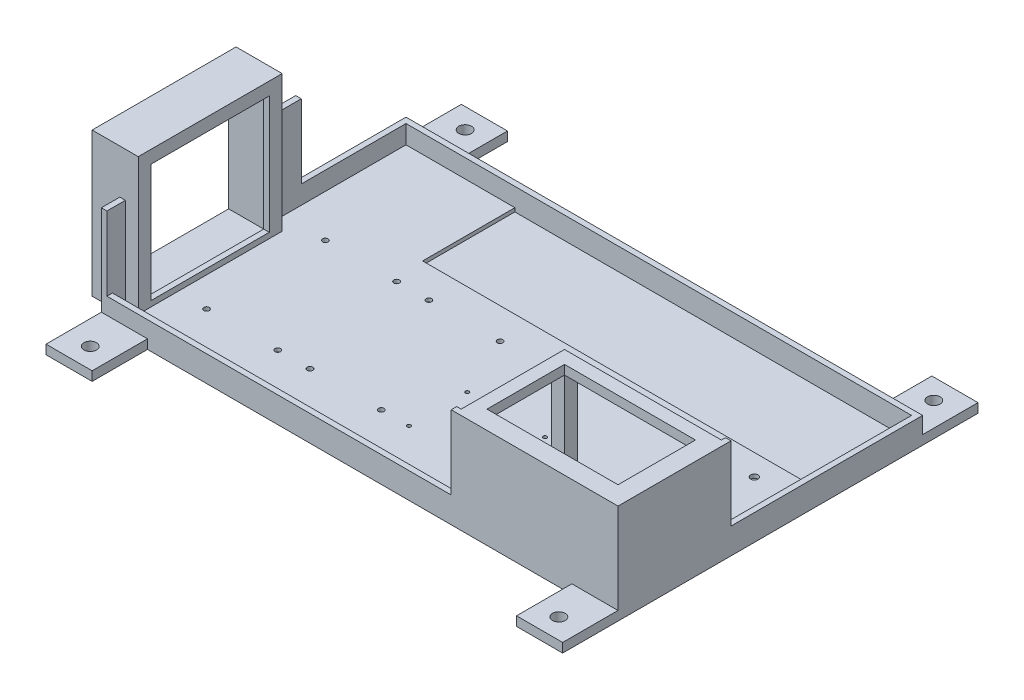
SolidWorks part; units mm, degrees
ref_plane "Front Plane" through (0, 0, 0) normal (0, 0, 1) x (1, 0, 0)
ref_plane "Top Plane" through (0, 0, 0) normal (0, 1, 0) x (1, 0, 0)
ref_plane "Right Plane" through (0, 0, 0) normal (1, 0, 0) x (0, 0, -1)
sketch "Sketch1" plane through (0, 0, 0) normal (0, 1, 0) x (1, 0, 0)
  line L1 (-140, -82.55) -> (140, -82.55)
  line L2 (-140, -82.55) -> (-140, 82.55)
  line L3 (-140, 82.55) -> (140, 82.55)
  line L4 (140, -82.55) -> (140, 82.55)
  line L5 (-140, -82.55) -> (140, 82.55) construction
  line L6 (-140, 82.55) -> (140, -82.55) construction
  point P0 (0, 0)
  dimension "D1" = 165.1
  dimension "D2" = 280
extrude "Floor" add sketch "Sketch1" along normal blind 4
sketch "Sketch2" plane through (0, 4, 0) normal (0, 1, 0) x (1, 0, 0)
  line L0 (137, -79.55) -> (137, 79.55)
  line L1 (137, 79.55) -> (-137, 79.55)
  line L2 (-137, 79.55) -> (-137, -79.55)
  line L3 (-137, -79.55) -> (137, -79.55)
  line L4 (140, -82.55) -> (140, 82.55)
  line L5 (140, 82.55) -> (-140, 82.55)
  line L6 (-140, 82.55) -> (-140, -82.55)
  line L7 (-140, -82.55) -> (140, -82.55)
  line L8 (140, -82.55) -> (140, 82.55)
  line L9 (140, 82.55) -> (-140, 82.55)
  line L10 (-140, 82.55) -> (-140, -82.55)
  line L11 (-140, -82.55) -> (140, -82.55)
  dimension "D1" = 0
  dimension "D2" = 3
extrude "Wall" add sketch "Sketch2" along normal blind 10
sketch "Sketch4" plane through (0, 4, 0) normal (0, 1, 0) x (1, 0, 0)
  line L0 (130, -30.55) -> (59, -30.55)
  line L1 (137, -79.55) -> (52, -79.55)
  line L2 (137, -79.55) -> (137, -23.55)
  line L3 (137, -23.55) -> (52, -23.55)
  line L4 (52, -79.55) -> (52, -23.55)
  line L5 (59, -72.55) -> (59, -30.55)
  line L6 (130, -72.55) -> (59, -72.55)
  line L7 (130, -72.55) -> (130, -30.55)
  dimension "D1" = 85
  dimension "D2" = 56
  dimension "D3" = 7
extrude "Rpi stand" add sketch "Sketch4" along normal blind 5 from offset 45
sketch "Sketch7" plane through (0, 14, 0) normal (0, 1, 0) x (1, 0, 0)
  line L0 (-137, 79.55) -> (-137, -79.55) construction
  line L1 (-140, -82.55) -> (-137, -82.55)
  line L2 (-140, -82.55) -> (-140, 22.7839)
  line L3 (-140, 22.7839) -> (-137, 22.7839)
  line L4 (-137, -82.55) -> (-137, 22.7839)
  line L5 (-137, -79.55) -> (137, -79.55) construction
  line L6 (140, -82.55) -> (49.6123, -82.55)
  line L7 (140, -82.55) -> (140, -79.55)
  line L8 (137, -79.55) -> (49.6123, -79.55)
  line L9 (49.6123, -82.55) -> (49.6123, -79.55)
  line L10 (137, -79.55) -> (137, 79.55) construction
  line L12 (140, -79.55) -> (140, -21.3069)
  line L13 (140, -21.3069) -> (137, -21.3069)
  line L14 (137, -79.55) -> (137, -21.3069)
  line L15 (-137, -79.55) -> (137, -79.55) construction
extrude "Temp support" add sketch "Sketch7" along normal blind 40
sketch "Sketch3" plane through (0, 0, 0) normal (0, 1, 0) x (1, 0, 0)
  line L0 (-127, 101.6) -> (127, 101.6) construction
  line L1 (-140, 82.55) -> (-115, 82.55)
  line L2 (-140, 82.55) -> (-140, 112.55)
  line L3 (-140, 112.55) -> (-115, 112.55)
  line L4 (-115, 82.55) -> (-115, 112.55)
  line L5 (140, 82.55) -> (115, 82.55)
  line L6 (140, 82.55) -> (140, 112.55)
  line L7 (140, 112.55) -> (115, 112.55)
  line L8 (115, 82.55) -> (115, 112.55)
  line L9 (-140, -82.55) -> (-115, -82.55)
  line L10 (-140, -82.55) -> (-140, -112.55)
  line L11 (-140, -112.55) -> (-115, -112.55)
  line L12 (-115, -82.55) -> (-115, -112.55)
  line L13 (140, -82.55) -> (115, -82.55)
  line L14 (140, -82.55) -> (140, -112.55)
  line L15 (140, -112.55) -> (115, -112.55)
  line L16 (115, -82.55) -> (115, -112.55)
  line L17 (127, 101.6) -> (127, -101.6) construction
  line L18 (127, -101.6) -> (-127, -101.6) construction
  line L19 (-127, -101.6) -> (-127, 101.6) construction
  line L20 (-140, 30.6215) -> (140, 30.6215) construction
  line L22 (140, -21.3069) -> (140, 82.55) construction
  line L23 (0, 101.6) -> (0, -101.6) construction
  line L24 (-140, 22.7839) -> (-140, -82.55) construction
  line L25 (140, -21.3069) -> (140, 82.55) construction
  line L26 (-137, -82.55) -> (49.6123, -82.55) construction
  circle A0 centre (-127, 101.6) radius 3.429
  circle A1 centre (127, 101.6) radius 3.429
  circle A2 centre (127, -101.6) radius 3.429
  circle A3 centre (-127, -101.6) radius 3.429
  point P28 (-127.5, -82.55)
  point P29 (-115, -97.55)
  point P30 (127.5, -82.55)
  point P31 (-115, 97.55)
  dimension "D5" = 6.858
  dimension "D1" = 25
  dimension "D2" = 25
  dimension "D3" = 30
  dimension "D4" = 30
  dimension "D6" = 203.2
  dimension "D7" = 254
extrude "Brackets" add sketch "Sketch3" along normal blind 5
sketch "Sketch5" plane through (-140, 0, 0) normal (-1, 0, 0) x (0, 0, 1)
  line L0 (-5.45, 78) -> (72.55, 78)
  line L1 (-1.45, 4) -> (68.55, 4)
  line L2 (-1.45, 4) -> (-1.45, 74)
  line L3 (-1.45, 74) -> (68.55, 74)
  line L4 (68.55, 4) -> (68.55, 74)
  line L5 (72.55, 0) -> (72.55, 78)
  line L6 (-5.45, 0) -> (72.55, 0)
  line L7 (-5.45, 0) -> (-5.45, 78)
  line L9 (112.55, 5) -> (112.55, 0) construction
  line L11 (-79.55, 4) -> (79.55, 4) construction
  dimension "D1" = 70
  dimension "D2" = 70
  dimension "D5" = 40
  dimension "D3" = 4
extrude "Fan Holder" add sketch "Sketch5" along normal blind 15 and the other way blind 10
sketch "Sketch8" plane through (-140, 0, 0) normal (-1, 0, 0) x (0, 0, 1)
  line L4 (-1.45, 54) -> (-1.45, 4)
  line L5 (-1.45, 4) -> (68.55, 4)
  line L6 (68.55, 4) -> (68.55, 54)
  line L7 (68.55, 54) -> (-1.45, 54)
  line L8 (-1.45, 54) -> (-1.45, 4)
  line L9 (-1.45, 4) -> (68.55, 4)
  line L10 (68.55, 4) -> (68.55, 54)
  line L15 (68.55, 54) -> (-1.45, 54)
  dimension "D1" = 0
extrude "Fan hole" cut sketch "Sketch8" against normal up to next (3 mm away)
sketch "Sketch11" plane through (-130, 0, 0) normal (-1, 0, 0) x (0, 0, 1)
  line L4 (-5.45, 78) -> (-5.45, 0)
  line L5 (-5.45, 0) -> (72.55, 0)
  line L6 (72.55, 0) -> (72.55, 78)
  line L7 (72.55, 78) -> (-5.45, 78)
  line L8 (-5.45, 78) -> (-5.45, 0)
  line L9 (-5.45, 0) -> (72.55, 0)
  line L10 (72.55, 0) -> (72.55, 78)
  line L11 (72.55, 78) -> (-5.45, 78)
  line L16 (1.55, 71) -> (1.55, 7)
  line L17 (1.55, 7) -> (65.55, 7)
  line L18 (65.55, 7) -> (65.55, 71)
  line L19 (65.55, 71) -> (1.55, 71)
  line L20 (1.55, 71) -> (1.55, 7)
  line L21 (1.55, 7) -> (65.55, 7)
  line L22 (65.55, 7) -> (65.55, 71)
  line L23 (65.55, 71) -> (1.55, 71)
  dimension "D1" = 0
  dimension "D2" = 7
extrude "Boss-Extrude9" add sketch "Sketch11" along normal blind 3
sketch "Sketch12" plane through (0, 49, 0) normal (0, -1, 0) x (1, 0, 0)
  line L1 (52, 23.55) -> (59, 23.55)
  line L2 (52, 23.55) -> (52, 30.55)
  line L3 (52, 30.55) -> (59, 30.55)
  line L4 (59, 23.55) -> (59, 30.55)
  dimension "D1" = 7
  dimension "D2" = 7
extrude "Boss-Extrude10" add sketch "Sketch12" along normal up to next
sketch "Sketch13" plane through (0, 4, 0) normal (0, 1, 0) x (1, 0, 0)
  line L0 (-137, -79.55) -> (137, -79.55) construction
  line L1 (-137, -82.55) -> (-137, -72.55) construction
  line L2 (-114, -51.55) -> (-114, 12.85) construction
  line L3 (-114, 12.85) -> (-75.4, 12.85) construction
  line L4 (-114, -51.55) -> (-75.4, -51.55) construction
  line L5 (-75.4, 12.85) -> (-75.4, -51.55) construction
  line L6 (-75.4, 12.85) -> (-57.9, 12.85) construction
  line L7 (-57.9, 12.85) -> (-57.9, -51.55) construction
  line L8 (-57.9, -51.55) -> (-19.3, -51.55) construction
  line L9 (-19.3, -51.55) -> (-19.3, 12.85) construction
  line L10 (-19.3, 12.85) -> (-57.9, 12.85) construction
  line L11 (-75.4, -51.55) -> (-57.9, -51.55) construction
  line L12 (-19.3, -51.55) -> (-4.3, -51.55) construction
  line L13 (-4.3, -51.55) -> (-4.3, -19.95) construction
  line L14 (-4.3, -19.95) -> (37.87, -19.95) construction
  line L15 (37.87, -19.95) -> (37.87, -51.55) construction
  line L16 (37.87, -51.55) -> (-4.3, -51.55) construction
  line L17 (111.34, 79.55) -> (111.34, 18.05) construction
  line L19 (137, 79.55) -> (-137, 79.55) construction
  line L20 (137, -21.3069) -> (137, 79.55) construction
  line L21 (111.34, 18.05) -> (113.34, 18.05) construction
  line L22 (111.34, 18.05) -> (34.84, 18.05) construction
  circle A0 centre (-114, -51.55) radius 1.5
  circle A1 centre (-114, 12.85) radius 1.5
  circle A2 centre (-75.4, 12.85) radius 1.5
  circle A3 centre (-75.4, -51.55) radius 1.5
  circle A4 centre (-57.9, 12.85) radius 1.5
  circle A5 centre (-57.9, -51.55) radius 1.5
  circle A6 centre (-19.3, -51.55) radius 1.5
  circle A7 centre (-19.3, 12.85) radius 1.5
  circle A8 centre (-4.3, -51.55) radius 1
  circle A9 centre (-4.3, -19.95) radius 1
  circle A10 centre (37.87, -19.95) radius 1
  circle A11 centre (37.87, -51.55) radius 1
  circle A12 centre (113.34, 18.05) radius 2
  circle A13 centre (34.84, 18.05) radius 2
  point P6 (-137, -77.55)
  dimension "D1" = 28
  dimension "D2" = 23
  dimension "D3" = 3
  dimension "D6" = 3
  dimension "D7" = 3
  dimension "D8" = 3
  dimension "D11" = 3
  dimension "D12" = 3
  dimension "D13" = 3
  dimension "D14" = 3
  dimension "D16" = 2
  dimension "D18" = 2
  dimension "D20" = 2
  dimension "D21" = 2
  dimension "D25" = 4
  dimension "D27" = 4
  dimension "D4" = 64.4
  dimension "D5" = 38.6
  dimension "D9" = 17.5
  dimension "D10" = 38.6
  dimension "D15" = 15
  dimension "D17" = 31.6
  dimension "D19" = 42.17
  dimension "D22" = 61.5
  dimension "D23" = 25.66
  dimension "D24" = 2
  dimension "D26" = 76.5
extrude "Cut-Extrude1" cut sketch "Sketch13" against normal blind 2
sketch "Sketch14" plane through (0, 4, 0) normal (0, 1, 0) x (1, 0, 0)
  line L0 (137, 79.55) -> (-78, 79.55)
  line L1 (137, 79.55) -> (-137, 79.55) construction
  line L2 (-78, 79.55) -> (-78, 29.55)
  line L3 (-78, 29.55) -> (137, 29.55)
  line L4 (137, -79.55) -> (137, 79.55) construction
  line L5 (137, 29.55) -> (137, 79.55)
  dimension "D1" = 215
  dimension "D2" = 50
extrude "Cut-Extrude2" cut sketch "Sketch14" against normal blind 2
equation "\"D2@Sketch3\"=\"D1@Sketch3\""
equation "\"D4@Sketch3\"=\"D3@Sketch3\""
